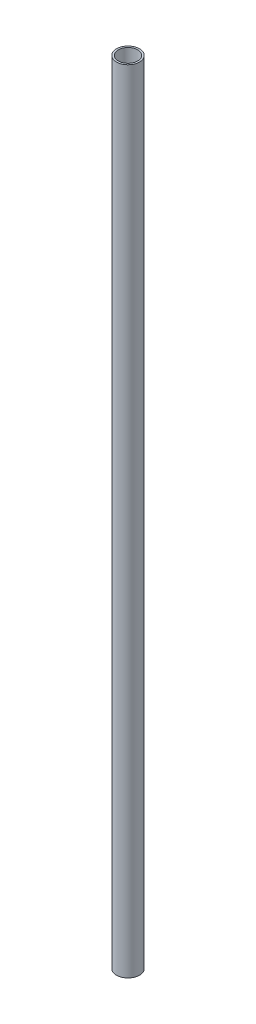
SolidWorks part; units mm, degrees
material "AISI 4130 Steel, annealed at 865C"
ref_plane "Front Plane" through (0, 0, 0) normal (0, 0, 1) x (1, 0, 0)
ref_plane "Top Plane" through (0, 0, 0) normal (0, 1, 0) x (1, 0, 0)
ref_plane "Right Plane" through (0, 0, 0) normal (1, 0, 0) x (0, 0, -1)
sketch "Sketch1" plane through (0, 0, 0) normal (0, 1, 0) x (1, 0, 0)
  circle A0 centre (0, 0) radius 6.6929
  circle A1 centre (0, 0) radius 7.9375
  dimension "D1" = 15.875
  dimension "D2" = 13.3858
extrude "Boss-Extrude1" add sketch "Sketch1" along normal blind 546.1
ref_axis "Axis1" through (0, 546.1, 0) along (0, -1, 0)
